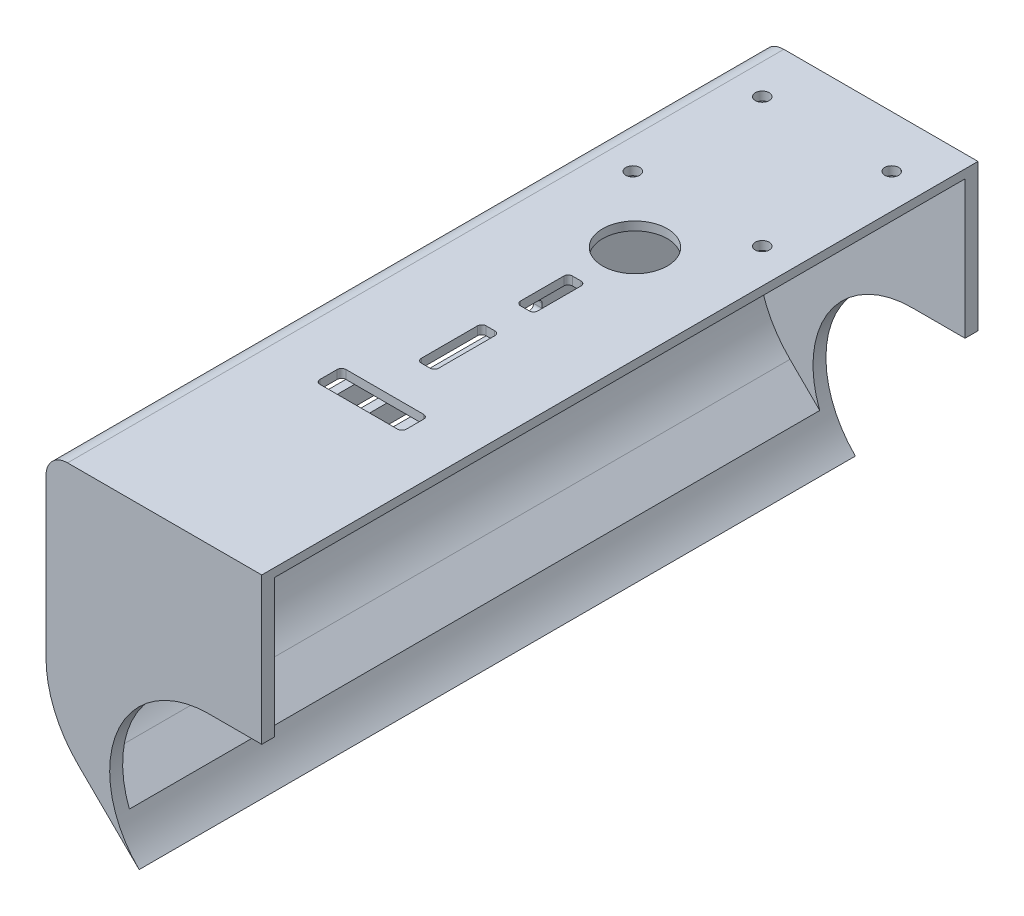
SolidWorks part; units mm, degrees
ref_plane "Front Plane" through (0, 0, 0) normal (0, 0, 1) x (1, 0, 0)
ref_plane "Top Plane" through (0, 0, 0) normal (0, 1, 0) x (1, 0, 0)
ref_plane "Right Plane" through (0, 0, 0) normal (1, 0, 0) x (0, 0, -1)
sketch "Sketch1" plane through (0, 0, 0) normal (0, 0, 1) x (1, 0, 0)
  line L0 (-176.4226, 3.6462) -> (-198.0073, 24.9918)
  line L1 (-198.0073, 24.9918) -> (-198.0073, 77)
  line L2 (-198.0073, 77) -> (-148.0073, 77)
  line L4 (-160.25, 43) -> (-148.0073, 43)
  line L6 (-148.0073, 43) -> (-148.0073, 77)
  arc A1 (-160.25, 43) -> (-176.4226, 3.6462) centre (-160.25, 20) ccw
extrude "Boss-Extrude1" add sketch "Sketch1" against normal blind 3
sketch "Sketch2" plane through (0, 0, -166) normal (0, 0, -1) x (-1, 0, 0)
  line L5 (198.0073, 24.9918) -> (198.0073, 77)
  line L6 (198.0073, 77) -> (148.0073, 77)
  line L7 (148.0073, 77) -> (148.0073, 43)
  line L8 (148.0073, 43) -> (160.25, 43)
  line L9 (176.4226, 3.6462) -> (198.0073, 24.9918)
  line L10 (198.0073, 24.9918) -> (198.0073, 77)
  line L11 (198.0073, 77) -> (148.0073, 77)
  line L12 (148.0073, 77) -> (148.0073, 43)
  line L13 (148.0073, 43) -> (160.25, 43)
  line L14 (176.4226, 3.6462) -> (198.0073, 24.9918)
  arc A1 (176.4226, 3.6462) -> (160.25, 43) centre (160.25, 20) ccw
  arc A2 (176.4226, 3.6462) -> (160.25, 43) centre (160.25, 20) ccw
  dimension "D1" = 0
extrude "Boss-Extrude2" add sketch "Sketch2" against normal blind 3 separate body
sketch "Sketch3" plane through (0, 0, -3) normal (0, 0, -1) x (-1, 0, 0)
  line L0 (181.6864, 11.6645) -> (196.0073, 25.8268)
  line L1 (196.0073, 25.8268) -> (196.0073, 75)
  line L2 (196.0073, 75) -> (148.0073, 75)
  line L3 (148.0073, 77) -> (148.0073, 75)
  line L4 (175.0163, 5.0683) -> (196.0073, 25.8268) construction
  line L5 (198.0073, 24.9918) -> (198.0073, 77)
  line L6 (198.0073, 77) -> (148.0073, 77)
  line L7 (148.0073, 77) -> (148.0073, 43)
  line L8 (148.0073, 43) -> (160.25, 43)
  line L9 (176.4226, 3.6462) -> (198.0073, 24.9918)
  line L10 (198.0073, 24.9918) -> (198.0073, 77)
  line L11 (198.0073, 77) -> (148.0073, 77)
  line L14 (176.4226, 3.6462) -> (198.0073, 24.9918)
  arc A0 (160.25, -3) -> (160.25, 43) centre (160.25, 20) ccw construction
  arc A1 (176.4226, 3.6462) -> (160.25, 43) centre (160.25, 20) ccw
  arc A3 (176.4226, 3.6462) -> (181.6864, 11.6645) centre (160.25, 20) ccw
  dimension "D1" = 0
  dimension "D2" = 2
extrude "Boss-Extrude3" add sketch "Sketch3" along normal up to surface (160 mm away) up to face at (-173.6482, 45.6762, -163)
fillet "Fillet1" radius 5 2 edges at (-198.0073, 77, -83) (-196.0073, 75, -83)
fillet "Fillet2" radius 25 2 edges at (-196.0073, 25.8268, -83) (-198.0073, 24.9918, -83)
sketch "Sketch4" plane through (-198.0073, 0, 0) normal (-1, 0, 0) x (0, 0, 1)
  line L0 (-83, 77) -> (-83, 3.6462) construction
  line L1 (-166, 77) -> (0, 77) construction
  line L2 (-166, 3.6462) -> (0, 3.6462) construction
  line L3 (-112, 59.5) -> (-54, 59.5)
  line L4 (-112, 67) -> (-54, 67)
  line L5 (-113, 66) -> (-113, 65)
  line L6 (-112, 64) -> (-54, 64)
  line L7 (-53, 66) -> (-53, 65)
  line L8 (-113, 58.5) -> (-113, 57.5)
  line L9 (-112, 56.5) -> (-54, 56.5)
  line L10 (-53, 58.5) -> (-53, 57.5)
  line L11 (-112, 52) -> (-54, 52)
  line L12 (-113, 51) -> (-113, 50)
  line L13 (-112, 49) -> (-54, 49)
  line L14 (-53, 51) -> (-53, 50)
  line L15 (-112, 44.5) -> (-54, 44.5)
  line L16 (-113, 43.5) -> (-113, 42.5)
  line L17 (-112, 41.5) -> (-54, 41.5)
  line L18 (-53, 43.5) -> (-53, 42.5)
  arc A0 (-54, 67) -> (-53, 66) centre (-54, 66) cw
  arc A1 (-54, 64) -> (-53, 65) centre (-54, 65) ccw
  arc A2 (-112, 67) -> (-113, 66) centre (-112, 66) ccw
  arc A3 (-113, 65) -> (-112, 64) centre (-112, 65) ccw
  arc A4 (-54, 59.5) -> (-53, 58.5) centre (-54, 58.5) cw
  arc A5 (-54, 56.5) -> (-53, 57.5) centre (-54, 57.5) ccw
  arc A6 (-112, 59.5) -> (-113, 58.5) centre (-112, 58.5) ccw
  arc A7 (-113, 57.5) -> (-112, 56.5) centre (-112, 57.5) ccw
  arc A8 (-54, 52) -> (-53, 51) centre (-54, 51) cw
  arc A9 (-54, 49) -> (-53, 50) centre (-54, 50) ccw
  arc A10 (-112, 52) -> (-113, 51) centre (-112, 51) ccw
  arc A11 (-113, 50) -> (-112, 49) centre (-112, 50) ccw
  arc A12 (-54, 44.5) -> (-53, 43.5) centre (-54, 43.5) cw
  arc A13 (-54, 41.5) -> (-53, 42.5) centre (-54, 42.5) ccw
  arc A14 (-112, 44.5) -> (-113, 43.5) centre (-112, 43.5) ccw
  arc A15 (-113, 42.5) -> (-112, 41.5) centre (-112, 42.5) ccw
  dimension "D1" = 1
  dimension "D2" = 4
extrude "Cut-Extrude1" cut sketch "Sketch4" against normal blind 5
sketch "Sketch5" plane through (0, 77, 0) normal (0, 1, 0) x (1, 0, 0)
  line L1 (-180.5073, 51) -> (-160.5073, 51)
  line L2 (-180.5073, 51) -> (-180.5073, 45)
  line L3 (-180.5073, 45) -> (-160.5073, 45)
  line L4 (-160.5073, 51) -> (-160.5073, 45)
  line L5 (-173.0073, 76) -> (-169.0073, 76)
  line L6 (-173.0073, 76) -> (-173.0073, 61)
  line L7 (-173.0073, 61) -> (-169.0073, 61)
  line L8 (-169.0073, 76) -> (-169.0073, 61)
  line L9 (-173.0073, 96) -> (-169.0073, 96)
  line L10 (-173.0073, 96) -> (-173.0073, 84)
  line L11 (-173.0073, 84) -> (-169.0073, 84)
  line L12 (-169.0073, 96) -> (-169.0073, 84)
  line L13 (-148.0073, 0) -> (-193.0073, 0) construction
  line L14 (-170.5073, 0) -> (-170.5073, 45) construction
  circle A0 centre (-170.5073, 109) radius 7.5
extrude "Cut-Extrude2" cut sketch "Sketch5" against normal blind 2
sketch "Sketch6" plane through (0, 77, 0) normal (0, 1, 0) x (1, 0, 0)
  circle A0 centre (-156.0073, 154) radius 1.6
  circle A1 centre (-156.0073, 124) radius 1.6
  circle A2 centre (-186.0073, 124) radius 1.6
  circle A3 centre (-186.0073, 154) radius 1.6
extrude "Cut-Extrude3" cut sketch "Sketch6" against normal up to surface (2 mm away) up to face at (-170.5073, 75, -48)
fillet "Fillet3" radius 1 12 edges at (-169.0073, 76, -76) (-173.0073, 76, -76) (-169.0073, 76, -84) (-173.0073, 76, -84) (-173.0073, 76, -96) (-169.0073, 76, -96) (-160.5073, 76, -45) (-160.5073, 76, -51) (-180.5073, 76, -51) (-180.5073, 76, -45) (-173.0073, 76, -61) (-169.0073, 76, -61)
